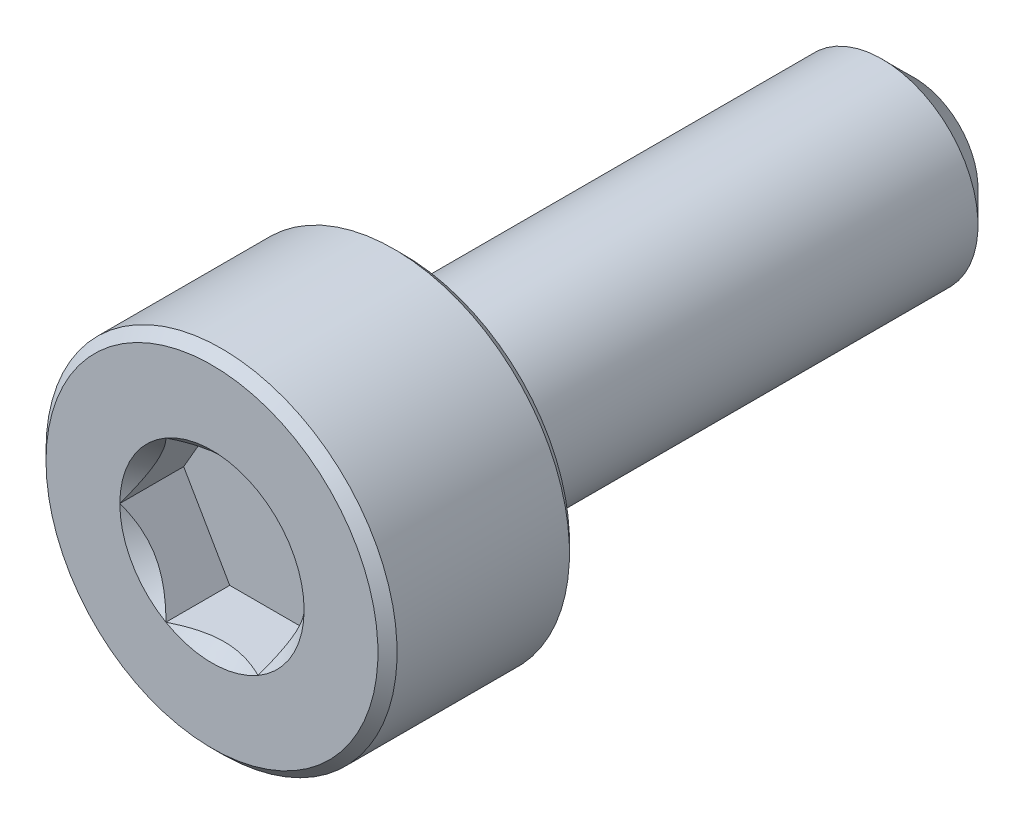
SolidWorks part; units mm, degrees
ref_plane "Front Plane" through (0, 0, 0) normal (0, 0, 1) x (1, 0, 0)
ref_plane "Top Plane" through (0, 0, 0) normal (0, 1, 0) x (1, 0, 0)
ref_plane "Right Plane" through (0, 0, 0) normal (1, 0, 0) x (0, 0, -1)
sketch "Sketch1" plane through (0, 0, 0) normal (1, 0, 0) x (0, 0, -1)
  line L0 (-5.5, 0) -> (5.5, 0) construction
  line L1 (5.5, 0) -> (5.5, 1) construction
  line L2 (5.5, 1) -> (5, 1.5) construction
  line L3 (5, 1.5) -> (-12.5, 1.5) construction
  line L5 (-2.5, 1.5) -> (-2.5, 2.75) construction
  line L6 (-2.5, 2.75) -> (-5.5, 2.75) construction
  line L7 (-5.5, 2.75) -> (-5.5, 0) construction
  line L8 (5.5, 1) -> (5.5, 1.5) construction
  line L9 (5.4688, 1.5541) -> (5.7188, 1.1211) construction
  line L10 (5.7188, 1.1211) -> (5.9688, 1.5541) construction
  line L11 (5.9688, 1.5541) -> (5.4688, 1.5541) construction
  line L12 (5.7188, 1.5541) -> (5.7188, 1.5) construction
  line L13 (5.7188, 1.1211) -> (5.7188, 1.1752) construction
  line L14 (5.6875, 1.1752) -> (5.75, 1.1752) construction
  line L15 (5.5, 1.5) -> (5.9375, 1.5) construction
  line L16 (5.4844, 1.5271) -> (5.9531, 1.5271) construction
  line L17 (5.5, 0) -> (5.5, -1.5) construction
  line L18 (-2.65, 2.75) -> (-2.5, 2.6) construction
  line L19 (-5.35, 2.75) -> (-5.5, 2.6) construction
  point P0 (-5.5, 1.25)
  point P3 (3.75, 1.5)
  point P4 (0, 0)
  point P22 (5.7188, 1.1752)
  point P24 (-12.5, 1.5)
  point P25 (5.7188, 1.5)
  point P28 (5.7188, 1.5271)
  point P29 (3.75, -1.5)
  point P31 (-4, 2.75)
  point P37 (-3.025, 2.75)
  point P38 (-5.275, 2.75)
  dimension "head height" = 3
  dimension "D1" = 45
  dimension "head dia" = 5.5
  dimension "thread dia" = 3
  dimension "drive size" = 2.5
  dimension "pitch" = 0.5
  dimension "D2" = 0.0625
  dimension "D3" = 0.5
  dimension "D4" = 1.75
  dimension "D7" = 0.15
  dimension "D8" = 0.15
  dimension "D9" = 0.15
  dimension "D10" = 0.075
  dimension "D11" = 0.375
  dimension "D12" = 18
  dimension "length" = 8
sketch "Sketch2" plane through (0, 0, 0) normal (1, 0, 0) x (0, 0, -1)
  line L1 (-5.35, 2.75) -> (-2.65, 2.75)
  line L4 (5, 1.5) -> (5.5, 1)
  line L5 (5.5, 1) -> (5.5, 0)
  line L6 (-2.65, 2.75) -> (-2.5, 2.6) construction
  line L7 (5.5, 0) -> (-5.5, 0)
  line L8 (-5.35, 2.75) -> (-5.5, 2.6) construction
  line L9 (-2.65, 2.75) -> (-2.5, 2.6)
  line L10 (-5.35, 2.75) -> (-5.5, 2.6)
  line L11 (-5.5, 2.6) -> (-5.5, 0)
  line L12 (-2.5, 2.6) -> (-2.5, 1.5)
  line L13 (-2.5, 1.5) -> (5, 1.5)
revolve "Revolve1" add sketch "Sketch2" angle 360 about L7
sketch "Sketch3" plane through (0, 0, 5.5) normal (0, 0, 1) x (1, 0, 0)
  line L1 (0.7217, 1.25) -> (-0.7217, 1.25)
  line L2 (-0.7217, 1.25) -> (-1.4434, 0)
  line L3 (-1.4434, 0) -> (-0.7217, -1.25)
  line L4 (-0.7217, -1.25) -> (0.7217, -1.25)
  line L5 (0.7217, -1.25) -> (1.4434, 0)
  line L6 (1.4434, 0) -> (0.7217, 1.25)
  circle A0 centre (0, 0) radius 1.25 construction
extrude "Cut-Extrude1" cut sketch "Sketch3" against normal offset from surface (1 mm away) 1 up to face at (-2.6, 0, 5.5)
sketch "Sketch4" plane through (0, 0, 5.5) normal (0, 0, 1) x (1, 0, 0)
  circle A0 centre (0, 0) radius 1.4434
extrude "Cut-Extrude2" cut sketch "Sketch4" against normal blind 0.5 draft 45
ref_plane "Plane1" [suppressed] through (0, 0, 12.5) normal (0, 0, 1) x (1, 0, 0)
split "Split1" [suppressed] bodies to split 106
sketch "Sketch6" [suppressed] plane through (0, 0, -5.5) normal (0, 0, -1) x (-1, 0, 0)
  circle A0 centre (0, 0) radius 1.5
curve "Helix/Spiral1" [suppressed] pitch 0.5 height 8.5 turns 17
sketch "Sketch7" [suppressed] plane through (0, 0, 0) normal (1, 0, 0) x (0, 0, -1)
  line L0 (5.4844, 1.5271) -> (5.9531, 1.5271)
  line L1 (5.9531, 1.5271) -> (5.75, 1.1752)
  line L2 (5.75, 1.1752) -> (5.6875, 1.1752)
  line L3 (5.6875, 1.1752) -> (5.4844, 1.5271)
sweep "Cut-Sweep1" [suppressed] cut profiles "Sketch7" path "Helix/Spiral1"
sketch "Sketch8" [suppressed] plane through (0, 0, 2.5) normal (0, 0, -1) x (-1, 0, 0)
  circle A0 centre (0, 0) radius 1.5
extrude "Boss-Extrude1" [suppressed] add sketch "Sketch8" along normal through all draft 45
ref_plane "Plane2" [suppressed] through (0, 0, 4) normal (0, 0, 1) x (1, 0, 0)
sketch "Sketch9" [suppressed] plane through (0, 0, 4) normal (0, 0, 1) x (1, 0, 0)
  line L0 (0, 2.6125) -> (0.048, 2.7496)
  line L1 (0, 2.6125) -> (-0.048, 2.7496)
  line L2 (0, 2.75) -> (0, 0) construction
  line L3 (-0.048, 2.7496) -> (0, 0) construction
  line L4 (0, 0) -> (0.048, 2.7496) construction
  arc A0 (0.048, 2.7496) -> (-0.048, 2.7496) centre (0, 0) ccw
  circle A1 centre (0, 0) radius 2.6125 construction
  dimension "D1" = 5.5
  dimension "D2" = 5.225
  dimension "D3" = 2
extrude "Cut-Extrude4" [suppressed] cut sketch "Sketch9" against normal up to vertex and the other way up to vertex
pattern_circular "CirPattern2" [suppressed] count 175 over 360 about axis through (0, 0, 5.5) along (0, 0, -1) of bodies 113
equation "\"D2@Sketch1\"=\"pitch@Sketch1\"/8"
equation "\"D3@Sketch1\"=\"pitch@Sketch1\""
equation "\"D3@Helix/Spiral1\"=\"length@Sketch1\"+\"pitch@Sketch1\""
equation "\"D4@Helix/Spiral1\"=\"pitch@Sketch1\""
equation "\"D4@Sketch1\"=\"pitch@Sketch1\"*3.5"
equation "\"D7@Sketch1\"=\"head height@Sketch1\"*.05"
equation "\"D8@Sketch1\"=\"D7@Sketch1\""
equation "\"D9@Sketch1\"=\"D7@Sketch1\""
equation "\"D10@Sketch1\"=\"D7@Sketch1\"/2"
equation "\"D11@Sketch1\"=\"D10@Sketch1\"*5"
equation "\"D2@Sketch9\"=\"D1@Sketch9\"*.95"
equation "\"D1@CirPattern2\"= ( 360 / \"D3@Sketch9\" ) - 5"
